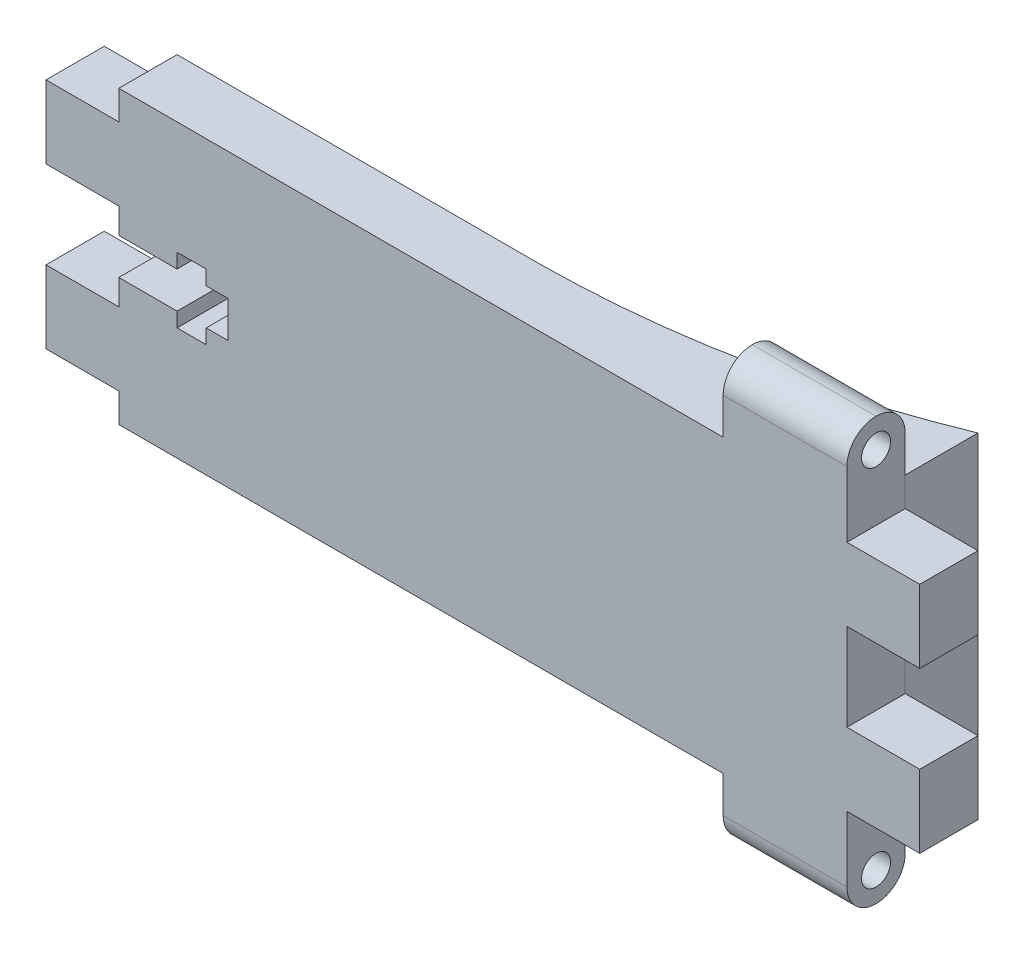
SolidWorks part; units mm, degrees
ref_plane "Front Plane" through (0, 0, 0) normal (0, 0, 1) x (1, 0, 0)
ref_plane "Top Plane" through (0, 0, 0) normal (0, 1, 0) x (1, 0, 0)
ref_plane "Right Plane" through (0, 0, 0) normal (1, 0, 0) x (0, 0, -1)
sketch "Sketch1" plane through (0, 0, 0) normal (0, 0, 1) x (1, 0, 0)
  line L5 (-38, 4.5) -> (-38, 2.5)
  line L6 (33, -20) -> (-50, -20)
  line L18 (0, 0) -> (0, -12.9172) construction
  line L42 (33, 20) -> (-50, 20)
  line L43 (-50, -20) -> (-50, -16)
  line L44 (50, -20) -> (-50, 20) construction
  line L45 (50, 20) -> (-50, -20) construction
  line L46 (-35, -2.5) -> (-38, -2.5)
  line L47 (-35, -2.5) -> (-35, 2.5)
  line L48 (-35, 2.5) -> (-38, 2.5)
  line L49 (-42, 4.5) -> (-42, 2.5)
  line L50 (-42, -4.5) -> (-38, -4.5)
  line L51 (-42, 4.5) -> (-38, 4.5)
  line L52 (-42, -2.5) -> (-50, -2.5)
  line L53 (-42, 2.5) -> (-50, 2.5)
  line L54 (-42, -2.5) -> (-42, -4.5)
  line L55 (-38, -2.5) -> (-38, -4.5)
  line L56 (0, 0) -> (-13.3376, 0) construction
  line L57 (-50, 2.5) -> (-50, 6)
  line L58 (-50, -16) -> (-60, -16)
  line L59 (-50, -6) -> (-60, -6)
  line L60 (-60, -16) -> (-60, -6)
  line L61 (-50, -6) -> (-50, -2.5)
  line L62 (-50, 16) -> (-60, 16)
  line L63 (-60, 16) -> (-60, 6)
  line L66 (-50, 6) -> (-60, 6)
  line L67 (-50, 16) -> (-50, 20)
  line L68 (50, -20) -> (50, -16)
  line L69 (50, -16) -> (60, -16)
  line L70 (60, -16) -> (60, -6)
  line L71 (50, -6) -> (60, -6)
  line L72 (50, -6) -> (50, -2.5)
  line L73 (50, -20) -> (50, -29)
  line L74 (50, -29) -> (33, -29)
  line L75 (33, -29) -> (33, -20)
  line L76 (50, 20) -> (50, 29)
  line L77 (50, 29) -> (33, 29)
  line L78 (33, 29) -> (33, 20)
  line L84 (50, 2.5) -> (50, 6)
  line L85 (50, 6) -> (60, 6)
  line L86 (60, 16) -> (60, 6)
  line L87 (50, 16) -> (60, 16)
  line L88 (50, 16) -> (50, 20)
  line L89 (50, 2.5) -> (50, -2.5)
  point P0 (0, 0)
  dimension "D15" = 17
  dimension "D1" = 40
  dimension "D2" = 100
  dimension "D3" = 17.5
  dimension "D4" = 22.5
  dimension "D5" = 15
  dimension "D6" = 3
  dimension "D7" = 4
  dimension "D8" = 9
  dimension "D9" = 15.5
  dimension "D10" = 4
  dimension "D11" = 10
  dimension "D12" = 10
  dimension "D13" = 17
  dimension "D14" = 9
  dimension "D16" = 9
  dimension "D17" = 0
  dimension "D18" = 0
extrude "Boss-Extrude1" add sketch "Sketch1" along normal blind 8 contours L42 L67 L62 L63 L66 L57 L53 L49 L51 L5 L48 L47 L46 L55 L50 L54 L52 L61 L59 L60 L58 L43 L6 L71 region at (3.581, 0, 0)
sketch "Sketch2" plane through (33, 0, 0) normal (-1, 0, 0) x (0, 0, 1)
  line L0 (8, -29) -> (0, -29) construction
  line L1 (0, -29) -> (0, -20) construction
  circle A0 centre (4, -25) radius 2
  dimension "D2" = 4
  dimension "D1" = 4
  dimension "D3" = 4
extrude "Cut-Extrude1" cut sketch "Sketch2" against normal blind 19
sketch "Sketch3" plane through (33, 0, 0) normal (-1, 0, 0) x (0, 0, 1)
  line L0 (8, 29) -> (8, 20) construction
  line L1 (8, 29) -> (0, 29) construction
  circle A0 centre (4, 25) radius 2
  dimension "D2" = 4
  dimension "D1" = 4
  dimension "D3" = 4
extrude "Cut-Extrude2" cut sketch "Sketch3" against normal blind 19
fillet "Fillet1" radius 4 4 edges at (41.5, -29, 8) (41.5, -29, 0) (41.5, 29, 8) (41.5, 29, 0)
sketch "Çizim2" plane through (0, 0, 0) normal (0, 1, 0) x (1, 0, 0)
  line L0 (50.0013, 0) -> (0.0013, 0)
  line L2 (50.0013, 0) -> (50.0013, 10)
  spline S0 degree 2 poles (0.0013, 0) (26.276, 0.2941) (50.0013, 10) knots 0 0 0 1 1 1
  dimension "D1" = 90
  dimension "D2" = 50
  dimension "D3" = 10
  dimension "D4" = 7.3126
  dimension "D5" = 7.1382
  dimension "D6" = 50.0013
extrude "Yükseklik-Ekstrüzyon1" add sketch "Çizim2" along normal mid plane 40
